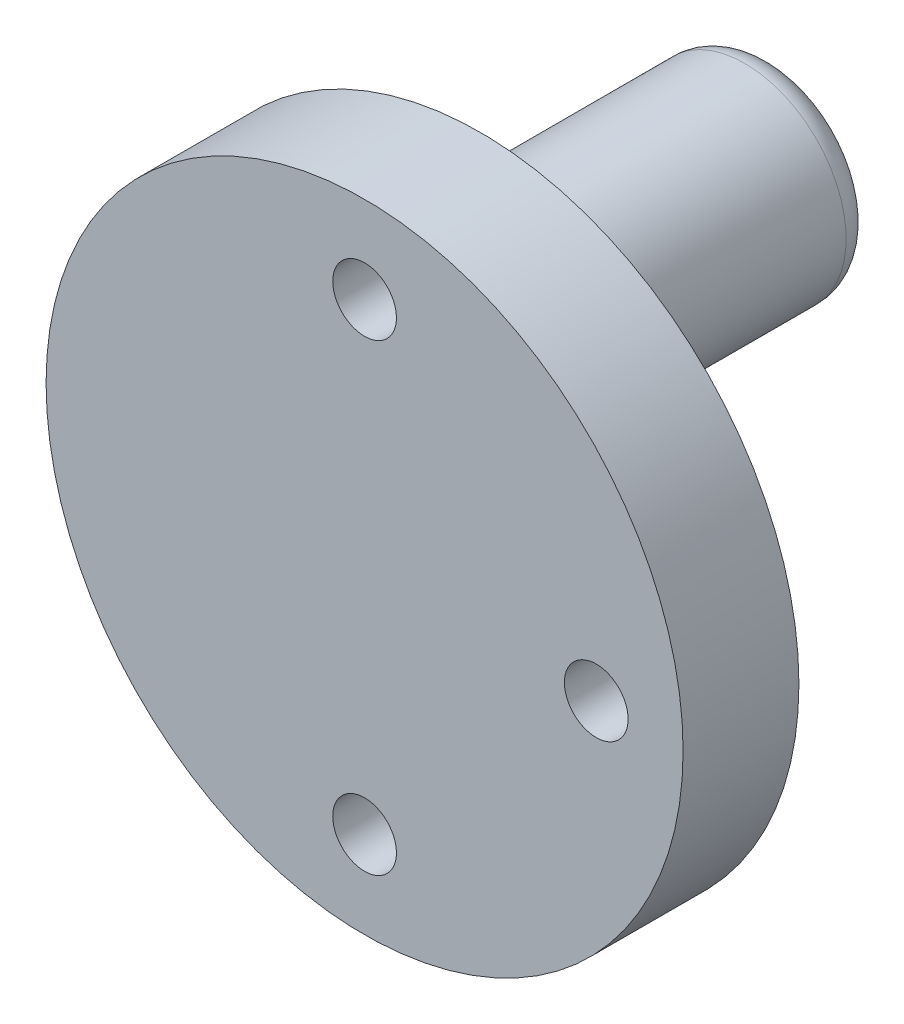
SolidWorks part; units mm, degrees
ref_plane "Front Plane" through (0, 0, 0) normal (0, 0, 1) x (1, 0, 0)
ref_plane "Top Plane" through (0, 0, 0) normal (0, 1, 0) x (1, 0, 0)
ref_plane "Right Plane" through (0, 0, 0) normal (1, 0, 0) x (0, 0, -1)
sketch "Sketch1" plane through (0, 0, 0) normal (0, 0, 1) x (1, 0, 0)
  circle A0 centre (0, 0) radius 11
  circle A1 centre (0, 8) radius 1.05
  circle A2 centre (8, 0) radius 1.05
  circle A3 centre (0, -8) radius 1.05
  circle A4 centre (-8, 0) radius 1.05 [skipped]
  dimension "D1" = 22
  dimension "D4" = 2.1
  dimension "D3" = 8
  dimension "D2" = 3
extrude "Boss-Extrude1" add sketch "Sketch1" along normal blind 4
sketch "Sketch9" plane through (0, 0, 0) normal (0, 0, -1) x (-1, 0, 0)
  circle A0 centre (5, 0) radius 6
  circle A2 centre (0, 0) radius 11 construction
  dimension "D1" = 12
extrude "Boss-Extrude2" add sketch "Sketch9" along normal blind 15.13
ref_plane "Plane1" through (0, 0, -15.13) normal (0, 0, -1) x (-1, 0, 0)
sketch "Sketch10" plane through (0, 0, -15.13) normal (0, 0, -1) x (-1, 0, 0)
  circle A0 centre (5, 0) radius 3.5
  dimension "D1" = 7
extrude "Cut-Extrude2" cut sketch "Sketch10" against normal blind 15 flip side to cut
fillet "Fillet1" radius 4.5 1 edges at (-11, 0, 0)
fillet "Fillet2" radius 1 1 edges at (-8.5, 0, -15.13)
ref_axis "O2" through (0, 0, 4) along (0, 0, -1)
fillet "Fillet4" radius 4 1 edges at (-8.5, 0, -0.13)
hole_wizard "CBORE for M2 SHCS1" positions "Sketch12" profile "Sketch11" counterbore size "M2" standard "Ansi Metric" end condition through all
sketch "Sketch12" plane through (0, 0, 0) normal (0, 0, -1) x (-1, 0, 0)
  point P0 (0, 8)
  point P1 (-8, 0)
  point P3 (0, -8)
sketch "Sketch11" plane through (0, 8, 0) normal (1, 0, 0) x (0, 1, 0)
  line L0 (0, 0) -> (0, 4)
  line L1 (0, 4) -> (1.1, 4)
  line L3 (1.1, 4) -> (1.1, 2)
  line L4 (1.1, 2) -> (2.2, 2)
  line L5 (2.2, 2) -> (2.2, 0)
  line L7 (2.2, 0) -> (0, 0)
  line L11 (0, -6.35) -> (0, 107.95) construction
  dimension "Thru Hole Dia." = 2.2
  dimension "Thru Hole Depth" = 4
  dimension "C'Bore Dia." = 4.4
  dimension "C'Bore Depth" = 2
ref_axis "A2" through (-5, 0, -3.8381) along (0, 0, -1)
ref_plane "OA2" through (0, 0, 0) normal (0, 1, 0) x (-1, 0, 0)
